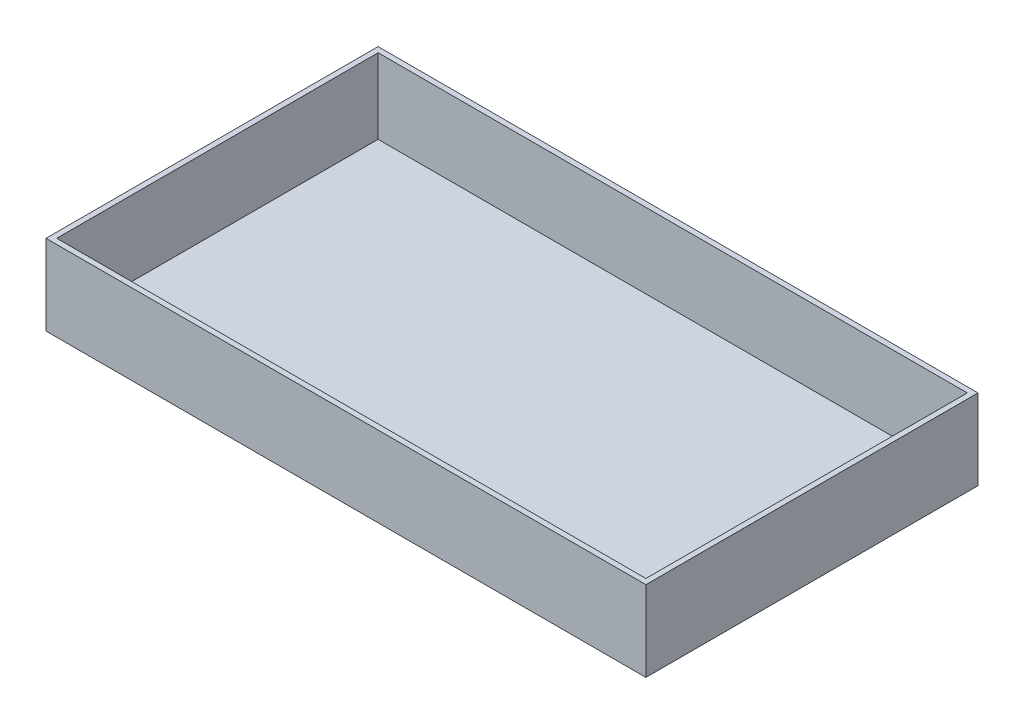
SolidWorks part; units mm, degrees
ref_plane "正面" through (0, 0, 0) normal (0, 0, 1) x (1, 0, 0)
ref_plane "平面" through (0, 0, 0) normal (0, 1, 0) x (1, 0, 0)
ref_plane "右側面" through (0, 0, 0) normal (1, 0, 0) x (0, 0, -1)
sketch "ｽｹｯﾁ1" plane through (0, 0, 0) normal (0, 1, 0) x (1, 0, 0)
  line L1 (-280, 155) -> (280, 155)
  line L2 (-280, 155) -> (-280, -155)
  line L3 (-280, -155) -> (280, -155)
  line L4 (280, 155) -> (280, -155)
  line L5 (-280, 155) -> (280, -155) construction
  line L6 (-280, -155) -> (280, 155) construction
  point P0 (0, 0)
  dimension "D1" = 310
  dimension "600" = 560
extrude "ﾎﾞｽ - 押し出し1" add sketch "ｽｹｯﾁ1" along normal blind 75
shell "ｼｪﾙ1" thickness 5 removed face at (0, 75, 0)
